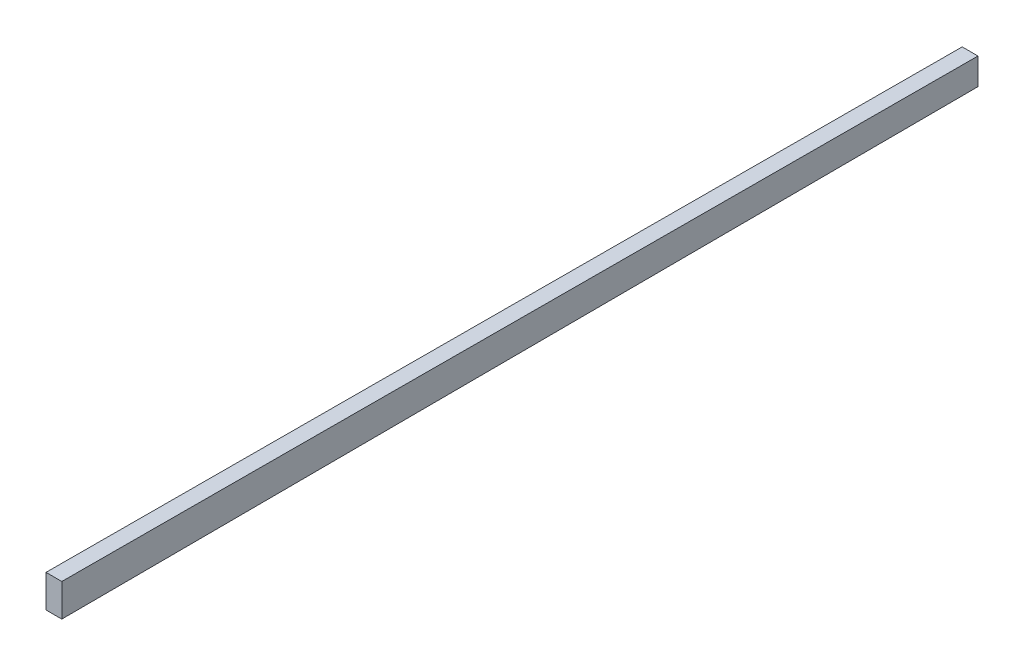
SolidWorks part; units mm, degrees
material "7050-T7651"
ref_plane "XY" through (0, 0, 0) normal (0, 0, 1) x (1, 0, 0)
ref_plane "XZ" through (0, 0, 0) normal (0, 1, 0) x (1, 0, 0)
ref_plane "YZ" through (0, 0, 0) normal (1, 0, 0) x (0, 0, -1)
ref_axis "X" through (-3.4925, 0, 0) along (1, 0, 0)
ref_axis "Y" through (0, -5.8674, 0) along (0, 1, 0)
ref_axis "Z" through (0, 0, 3.4925) along (0, 0, -1)
sketch "Sketch1" plane through (0, 0, 0) normal (0, 0, 1) x (1, 0, 0)
  line L1 (-3.175, -5.334) -> (3.175, -5.334)
  line L2 (-3.175, -5.334) -> (-3.175, 5.334)
  line L3 (-3.175, 5.334) -> (3.175, 5.334)
  line L4 (3.175, -5.334) -> (3.175, 5.334)
  line L5 (-3.175, -5.334) -> (3.175, 5.334) construction
  line L6 (-3.175, 5.334) -> (3.175, -5.334) construction
  point P0 (0, 0)
  dimension "D1" = 6.35
  dimension "D2" = 10.668
ref_plane "Plane1" through (0, 0, 368.3) normal (0, 0, 1) x (1, 0, 0)
sketch "Sketch2" plane through (0, 0, 368.3) normal (0, 0, 1) x (1, 0, 0)
  line L0 (-3.175, 5.334) -> (3.175, 5.334) construction
  line L1 (-3.175, -6.5532) -> (3.175, -6.5532)
  line L2 (-3.175, -6.5532) -> (-3.175, 6.5532)
  line L3 (-3.175, 6.5532) -> (3.175, 6.5532)
  line L4 (3.175, -6.5532) -> (3.175, 6.5532)
  line L5 (-3.175, -6.5532) -> (3.175, 6.5532) construction
  line L6 (-3.175, 6.5532) -> (3.175, -6.5532) construction
  point P0 (0, 0)
  dimension "D1" = 13.1064
loft "Loft1" add profiles "Sketch1", "Sketch2" connector at (-3.175, -5.334, 0) connector at (-3.175, -6.5532, 368.3)
